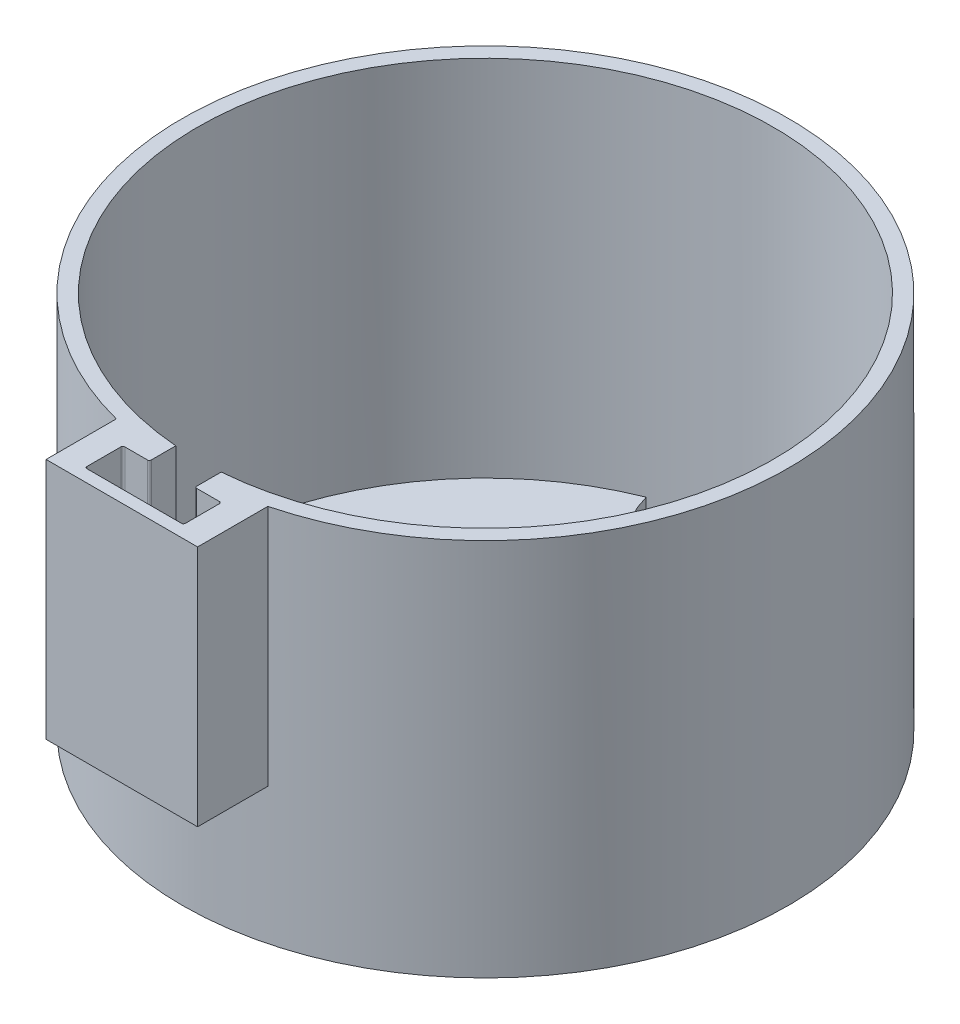
SolidWorks part; units mm, degrees
ref_plane "Front Plane" through (0, 0, 0) normal (0, 0, 1) x (1, 0, 0)
ref_plane "Top Plane" through (0, 0, 0) normal (0, 1, 0) x (1, 0, 0)
ref_plane "Right Plane" through (0, 0, 0) normal (1, 0, 0) x (0, 0, -1)
sketch "Sketch1" plane through (0, 0, 0) normal (0, 1, 0) x (1, 0, 0)
  circle A0 centre (0, 0) radius 40
extrude "Boss-Extrude1" add sketch "Sketch1" along normal blind 40 contours A0
sketch "Sketch2" plane through (0, 40, 0) normal (0, 1, 0) x (1, 0, 0)
  circle A0 centre (0, 0) radius 38
extrude "Cut-Extrude1" cut sketch "Sketch2" against normal blind 38
sketch "Sketch3" plane through (0, 2, 0) normal (0, 1, 0) x (1, 0, 0)
  arc A0 (-14.0761, 35.2968) -> (14.0761, 35.2968) centre (0, 39.1212) ccw
  circle A1 centre (0, 0) radius 38 construction
  circle A2 centre (0, 0) radius 38 construction
  arc A3 (-14.0761, 35.2968) -> (14.0761, 35.2968) centre (0, 0) cw
extrude "Cut-Extrude2" cut sketch "Sketch3" against normal blind 38
sketch "Sketch4" plane through (0, 2, 0) normal (0, 1, 0) x (1, 0, 0)
  circle A0 centre (0, 0) radius 5
extrude "Cut-Extrude3" cut sketch "Sketch4" against normal blind 38
sketch "Sketch6" plane through (0, 0, 0) normal (0, -1, 0) x (1, 0, 0)
  circle A1 centre (-20, 0) radius 2
  circle A2 centre (20, 0) radius 2
extrude "Boss-Extrude2" add sketch "Sketch6" along normal blind 2
sketch "Sketch9" plane through (0, 40, 0) normal (0, 1, 0) x (1, 0, 0)
  circle A3 centre (0, 0) radius 40
  circle A4 centre (0, 0) radius 40
  circle A6 centre (0, 0) radius 38 construction
  circle A7 centre (0, 0) radius 38
  dimension "D1" = 0
extrude "Boss-Extrude3" add sketch "Sketch9" along normal blind 10
sketch "Sketch10" plane through (0, 50, 0) normal (0, 1, 0) x (1, 0, 0)
  line L0 (0, 0) -> (0, -38) construction
  line L4 (0, -38) -> (10, -38)
  line L6 (10, -38) -> (10, -48)
  line L8 (0, -38) -> (-10, -38)
  line L9 (-10, -38) -> (-10, -48)
  line L10 (-10, -48) -> (10, -48)
  circle A0 centre (0, 0) radius 38 construction
extrude "Boss-Extrude4" add sketch "Sketch10" against normal blind 32 contours L8 L9 L10 L6 L4
sketch "Sketch11" plane through (0, 50, 0) normal (0, 1, 0) x (1, 0, 0)
  line L0 (0, -48) -> (0, -38) construction
  line L1 (-10, -48) -> (10, -48) construction
  line L2 (-10, -43.3649) -> (10, -43.3649) construction
  line L3 (-10, -38.7298) -> (-10, -48) construction
  line L4 (10, -38.7298) -> (10, -48) construction
  line L8 (-3, -36.8649) -> (3, -36.8649)
  line L10 (-3, -36.8649) -> (-3, -41.3649)
  line L11 (3, -36.8649) -> (3, -41.3649)
  line L12 (3, -41.3649) -> (6.5, -41.3649)
  line L13 (6.5, -41.3649) -> (6.5, -46.3649)
  line L14 (-3, -41.3649) -> (-6.5, -41.3649)
  line L15 (-6.5, -41.3649) -> (-6.5, -46.3649)
  line L16 (-6.5, -46.3649) -> (6.5, -46.3649)
  arc A0 (-14.0761, 35.2968) -> (14.0761, 35.2968) centre (0, 0) ccw construction
  dimension "D1" = 13
  dimension "D2" = 5
  dimension "D3" = 4.5
  dimension "D4" = 6
extrude "Cut-Extrude4" cut sketch "Sketch11" against normal blind 30
fillet "Fillet1" radius 0.25 6 edges at (-3, 35, 41.3649) (3, 35, 41.3649) (6.5, 35, 41.3649) (-6.5, 35, 41.3649) (6.5, 35, 46.3649) (-6.5, 35, 46.3649)
sketch "Sketch13" plane through (0, 0, 0) normal (0, -1, 0) x (1, 0, 0)
  circle A0 centre (-30, 0) radius 3
  circle A1 centre (30, 0) radius 3
extrude "Cut-Extrude5" cut sketch "Sketch13" against normal blind 10
